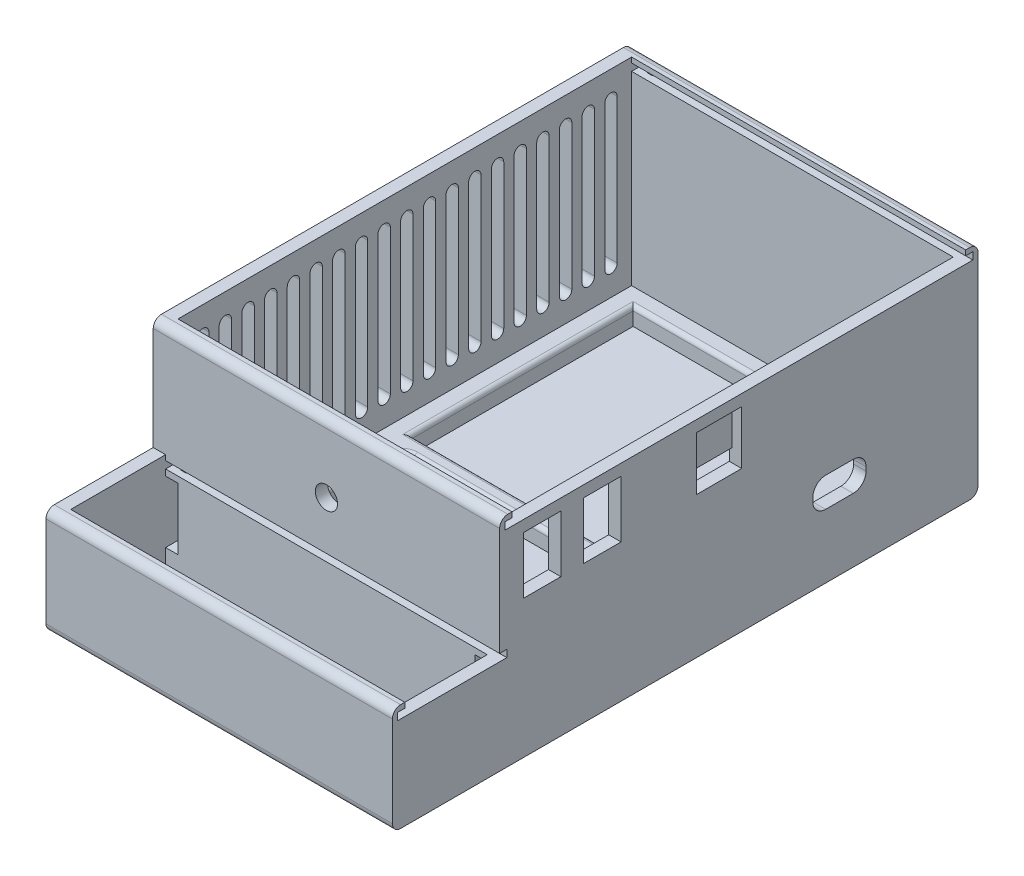
SolidWorks part; units mm, degrees
ref_plane "Front Plane" through (0, 0, 0) normal (0, 0, 1) x (1, 0, 0)
ref_plane "Top Plane" through (0, 0, 0) normal (0, 1, 0) x (1, 0, 0)
ref_plane "Right Plane" through (0, 0, 0) normal (1, 0, 0) x (0, 0, -1)
sketch "Sketch1" plane through (0, 0, 0) normal (0, 1, 0) x (1, 0, 0)
  line L5 (0, 0) -> (100, 0)
  line L6 (0, 0) -> (0, 150)
  line L7 (0, 150) -> (100, 150)
  line L8 (100, 0) -> (100, 150)
  dimension "D1" = 100
  dimension "D2" = 150
extrude "Boss-Extrude1" add sketch "Sketch1" against normal blind 5
sketch "Sketch2" plane through (0, 0, 0) normal (0, 1, 0) x (1, 0, 0)
  line L0 (0, 150) -> (0, 0) construction
  line L1 (11, 11) -> (89, 11)
  line L2 (11, 11) -> (11, 34)
  line L3 (11, 34) -> (89, 34)
  line L4 (89, 11) -> (89, 34)
  line L5 (0, 0) -> (100, 0) construction
  dimension "D1" = 78
  dimension "D2" = 23
  dimension "D3" = 11
  dimension "D4" = 11
extrude "Cut-Extrude1" cut sketch "Sketch2" against normal blind 2.5
sketch "Sketch3" plane through (0, 0, 0) normal (0, 1, 0) x (1, 0, 0)
  line L0 (11, 34) -> (89, 34)
  line L1 (89, 34) -> (89, 11)
  line L2 (89, 11) -> (11, 11)
  line L3 (11, 11) -> (11, 34)
  line L4 (8, 8) -> (8, 37)
  line L5 (8, 37) -> (92, 37)
  line L6 (92, 37) -> (92, 8)
  line L7 (92, 8) -> (8, 8)
  dimension "D1" = 3
extrude "Boss-Extrude2" add sketch "Sketch3" along normal blind 18
sketch "Sketch4" plane through (0, 0, 0) normal (0, 1, 0) x (1, 0, 0)
  line L0 (17.27, 44) -> (79.94, 44)
  line L1 (79.94, 44) -> (79.94, 46.79) construction
  line L2 (82.73, 46.79) -> (82.73, 82.03)
  line L3 (92, 37) -> (8, 37) construction
  line L4 (82.73, 82.03) -> (79.94, 82.03) construction
  line L5 (17.27, 44) -> (17.27, 82.0525)
  line L7 (17.27, 82.0525) -> (20.06, 82.0525) construction
  line L8 (17.27, 63.0262) -> (0, 63.0262) construction
  line L9 (20.06, 84.8425) -> (79.94, 84.82)
  line L10 (20.06, 84.8425) -> (20.06, 82.0525) construction
  line L11 (79.94, 82.03) -> (79.94, 84.82) construction
  line L13 (0, 150) -> (0, 0) construction
  line L14 (82.73, 64.41) -> (100, 64.41) construction
  line L15 (100, 0) -> (100, 150) construction
  arc A0 (79.94, 44) -> (82.73, 46.79) centre (79.94, 46.79) ccw
  arc A1 (82.73, 82.03) -> (79.94, 84.82) centre (79.94, 82.03) ccw
  arc A5 (17.27, 82.0525) -> (20.06, 84.8425) centre (20.06, 82.0525) cw
  dimension "D1" = 62.67
  dimension "D2" = 2.79
  dimension "D3" = 35.24
  dimension "D4" = 7
  dimension "D5" = 2.79
  dimension "D7" = 2.79
  dimension "D8" = 38.0525
extrude "Cut-Extrude2" cut sketch "Sketch4" against normal blind 4.25 contours L0 A0 L2 A1 L9 A5 L5
sketch "Sketch7" plane through (0, -2.5, 0) normal (0, 1, 0) x (1, 0, 0)
  line L0 (11, 34) -> (34, 11)
  line L1 (11, 11) -> (89, 11) construction
  line L2 (12, 34) -> (35, 11)
  line L3 (12, 34) -> (13, 34)
  line L5 (11, 11) -> (11.5217, 11)
  line L6 (89, 34) -> (89, 33)
  line L7 (13, 34) -> (36, 11)
  line L8 (14, 34) -> (37, 11)
  line L9 (15, 34) -> (38, 11)
  line L10 (16, 34) -> (39, 11)
  line L11 (17, 34) -> (40, 11)
  line L12 (18, 34) -> (41, 11)
  line L13 (19, 34) -> (42, 11)
  line L14 (20, 34) -> (43, 11)
  line L15 (21, 34) -> (44, 11)
  line L16 (22, 34) -> (45, 11)
  line L17 (23, 34) -> (46, 11)
  line L18 (24, 34) -> (47, 11)
  line L19 (25, 34) -> (48, 11)
  line L20 (26, 34) -> (49, 11)
  line L21 (27, 34) -> (50, 11)
  line L22 (28, 34) -> (51, 11)
  line L23 (29, 34) -> (52, 11)
  line L24 (30, 34) -> (53, 11)
  line L25 (31, 34) -> (54, 11)
  line L26 (32, 34) -> (55, 11)
  line L27 (33, 34) -> (56, 11)
  line L28 (34, 34) -> (57, 11)
  line L29 (35, 34) -> (58, 11)
  line L30 (36, 34) -> (59, 11)
  line L31 (37, 34) -> (60, 11)
  line L32 (38, 34) -> (61, 11)
  line L33 (39, 34) -> (62, 11)
  line L34 (40, 34) -> (63, 11)
  line L35 (41, 34) -> (64, 11)
  line L36 (42, 34) -> (65, 11)
  line L37 (43, 34) -> (66, 11)
  line L38 (44, 34) -> (67, 11)
  line L39 (45, 34) -> (68, 11)
  line L40 (46, 34) -> (69, 11)
  line L41 (47, 34) -> (70, 11)
  line L42 (48, 34) -> (71, 11)
  line L43 (49, 34) -> (72, 11)
  line L44 (50, 34) -> (73, 11)
  line L45 (51, 34) -> (74, 11)
  line L46 (52, 34) -> (75, 11)
  line L47 (53, 34) -> (76, 11)
  line L48 (54, 34) -> (77, 11)
  line L49 (55, 34) -> (78, 11)
  line L50 (56, 34) -> (79, 11)
  line L51 (57, 34) -> (80, 11)
  line L52 (58, 34) -> (81, 11)
  line L53 (59, 34) -> (82, 11)
  line L54 (60, 34) -> (83, 11)
  line L55 (61, 34) -> (84, 11)
  line L56 (62, 34) -> (85, 11)
  line L57 (63, 34) -> (86, 11)
  line L58 (64, 34) -> (87, 11)
  line L59 (65, 34) -> (88, 11)
  line L60 (66, 34) -> (89, 11)
  line L61 (67, 34) -> (89, 12)
  line L62 (68, 34) -> (89, 13)
  line L63 (69, 34) -> (89, 14)
  line L64 (70, 34) -> (89, 15)
  line L65 (71, 34) -> (89, 16)
  line L66 (72, 34) -> (89, 17)
  line L67 (73, 34) -> (89, 18)
  line L68 (74, 34) -> (89, 19)
  line L69 (75, 34) -> (89, 20)
  line L70 (76, 34) -> (89, 21)
  line L71 (77, 34) -> (89, 22)
  line L72 (78, 34) -> (89, 23)
  line L73 (79, 34) -> (89, 24)
  line L74 (80, 34) -> (89, 25)
  line L75 (81, 34) -> (89, 26)
  line L76 (82, 34) -> (89, 27)
  line L77 (83, 34) -> (89, 28)
  line L78 (84, 34) -> (89, 29)
  line L79 (85, 34) -> (89, 30)
  line L80 (86, 34) -> (89, 31)
  line L81 (87, 34) -> (89, 32)
  line L82 (88, 34) -> (89, 33)
  line L83 (11, 32.9783) -> (32.9783, 11)
  line L84 (11, 31.9565) -> (31.9565, 11)
  line L85 (11, 30.9348) -> (30.9348, 11)
  line L86 (11, 29.913) -> (29.913, 11)
  line L87 (11, 28.8913) -> (28.8913, 11)
  line L88 (11, 27.8696) -> (27.8696, 11)
  line L89 (11, 26.8478) -> (26.8478, 11)
  line L90 (11, 25.8261) -> (25.8261, 11)
  line L91 (11, 24.8043) -> (24.8043, 11)
  line L92 (11, 23.7826) -> (23.7826, 11)
  line L93 (11, 22.7609) -> (22.7609, 11)
  line L94 (11, 21.7391) -> (21.7391, 11)
  line L95 (11, 20.7174) -> (20.7174, 11)
  line L96 (11, 19.6956) -> (19.6956, 11)
  line L97 (11, 18.6739) -> (18.6739, 11)
  line L98 (11, 17.6522) -> (17.6522, 11)
  line L99 (11, 16.6304) -> (16.6304, 11)
  line L100 (11, 15.6087) -> (15.6087, 11)
  line L101 (11, 14.5869) -> (14.5869, 11)
  line L102 (11, 13.5652) -> (13.5652, 11)
  line L103 (11, 12.5435) -> (12.5435, 11)
  line L104 (11, 11.5217) -> (11.5217, 11)
  line L105 (12.5435, 11) -> (13.5652, 11)
  line L106 (11, 11.5217) -> (11, 11)
  line L107 (14.5869, 11) -> (15.6087, 11)
  line L108 (11, 13.5652) -> (11, 12.5435)
  line L110 (16.6304, 11) -> (17.6522, 11)
  line L111 (11, 16.6304) -> (11, 17.6522)
  line L112 (11, 18.6739) -> (11, 19.6956)
  line L113 (18.6739, 11) -> (19.6956, 11)
  line L114 (20.7174, 11) -> (21.7391, 11)
  line L115 (11, 20.7174) -> (11, 21.7391)
  line L116 (22.7609, 11) -> (23.7826, 11)
  line L117 (11, 22.7609) -> (11, 23.7826)
  line L118 (11, 24.8043) -> (11, 25.8261)
  line L119 (24.8043, 11) -> (25.8261, 11)
  line L120 (26.8478, 11) -> (27.8696, 11)
  line L121 (11, 26.8478) -> (11, 27.8696)
  line L122 (11, 28.8913) -> (11, 29.913)
  line L123 (11, 30.9348) -> (11, 31.9565)
  line L124 (28.8913, 11) -> (29.913, 11)
  line L125 (30.9348, 11) -> (31.9565, 11)
  line L126 (32.9783, 11) -> (34, 11)
  line L127 (35, 11) -> (36, 11)
  line L128 (11, 32.9783) -> (11, 34)
  line L129 (14, 34) -> (15, 34)
  line L130 (16, 34) -> (17, 34)
  line L131 (37, 11) -> (38, 11)
  line L132 (39, 11) -> (40, 11)
  line L133 (41, 11) -> (42, 11)
  line L134 (43, 11) -> (44, 11)
  line L135 (45, 11) -> (46, 11)
  line L136 (47, 11) -> (48, 11)
  line L137 (49, 11) -> (50, 11)
  line L138 (51, 11) -> (52, 11)
  line L139 (53, 11) -> (54, 11)
  line L140 (55, 11) -> (56, 11)
  line L141 (57, 11) -> (58, 11)
  line L142 (59, 11) -> (60, 11)
  line L143 (61, 11) -> (62, 11)
  line L144 (63, 11) -> (64, 11)
  line L145 (65, 11) -> (66, 11)
  line L146 (18, 34) -> (19, 34)
  line L147 (20, 34) -> (21, 34)
  line L148 (22, 34) -> (23, 34)
  line L149 (24, 34) -> (25, 34)
  line L150 (26, 34) -> (27, 34)
  line L151 (28, 34) -> (29, 34)
  line L152 (30, 34) -> (31, 34)
  line L153 (32, 34) -> (33, 34)
  line L154 (34, 34) -> (35, 34)
  line L155 (36, 34) -> (37, 34)
  line L156 (38, 34) -> (39, 34)
  line L157 (40, 34) -> (41, 34)
  line L158 (42, 34) -> (43, 34)
  line L159 (44, 34) -> (45, 34)
  line L160 (46, 34) -> (47, 34)
  line L161 (67, 11) -> (68, 11)
  line L162 (69, 11) -> (70, 11)
  line L163 (71, 11) -> (72, 11)
  line L164 (73, 11) -> (74, 11)
  line L165 (75, 11) -> (76, 11)
  line L166 (77, 11) -> (78, 11)
  line L167 (79, 11) -> (80, 11)
  line L168 (81, 11) -> (82, 11)
  line L169 (83, 11) -> (84, 11)
  line L170 (85, 11) -> (86, 11)
  line L171 (87, 11) -> (88, 11)
  line L172 (48, 34) -> (49, 34)
  line L173 (50, 34) -> (51, 34)
  line L174 (52, 34) -> (53, 34)
  line L175 (54, 34) -> (55, 34)
  line L176 (56, 34) -> (57, 34)
  line L177 (58, 34) -> (59, 34)
  line L178 (60, 34) -> (61, 34)
  line L179 (62, 34) -> (63, 34)
  line L180 (64, 34) -> (65, 34)
  line L181 (66, 34) -> (67, 34)
  line L182 (68, 34) -> (69, 34)
  line L183 (70, 34) -> (71, 34)
  line L184 (72, 34) -> (73, 34)
  line L185 (74, 34) -> (75, 34)
  line L186 (76, 34) -> (77, 34)
  line L187 (78, 34) -> (79, 34)
  line L188 (80, 34) -> (81, 34)
  line L189 (82, 34) -> (83, 34)
  line L190 (84, 34) -> (85, 34)
  line L191 (86, 34) -> (87, 34)
  line L192 (88, 34) -> (89, 34)
  line L193 (89, 12) -> (89, 11)
  line L194 (89, 14) -> (89, 13)
  line L195 (89, 16) -> (89, 15)
  line L196 (89, 18) -> (89, 17)
  line L197 (89, 20) -> (89, 19)
  line L198 (89, 22) -> (89, 21)
  line L199 (89, 24) -> (89, 23)
  line L200 (89, 26) -> (89, 25)
  line L201 (89, 28) -> (89, 27)
  line L202 (89, 30) -> (89, 29)
  line L203 (89, 32) -> (89, 31)
  line L204 (11, 15.6087) -> (11, 14.5869)
  dimension "D1" = 78
  dimension "D2" = 23
extrude "Cut-Extrude3" cut sketch "Sketch7" against normal blind 0.5
sketch "Sketch8" plane through (0, 0, -37) normal (0, 0, -1) x (-1, 0, 0)
  line L0 (-92, 18) -> (-92, 0) construction
  line L1 (-89, 1.5) -> (-86, 1.5)
  line L2 (-89, 1.5) -> (-89, 16.5)
  line L3 (-89, 16.5) -> (-86, 16.5)
  line L4 (-86, 1.5) -> (-86, 16.5)
  line L5 (-92, 18) -> (-8, 18) construction
  line L6 (-92, 0) -> (-8, 0) construction
  line L7 (-92, 18) -> (-8, 18) construction
  line L8 (-50, 18) -> (-50, 0) construction
  line L9 (-11, 16.5) -> (-14, 16.5)
  line L10 (-14, 1.5) -> (-14, 16.5)
  line L11 (-11, 1.5) -> (-14, 1.5)
  line L12 (-11, 1.5) -> (-11, 16.5)
  dimension "D1" = 3
  dimension "D2" = 1.5
  dimension "D3" = 1.5
  dimension "D4" = 3
extrude "Cut-Extrude4" cut sketch "Sketch8" against normal blind 3
sketch "Sketch9" plane through (8, 0, 0) normal (-1, 0, 0) x (0, 0, 1)
  line L0 (-37, 18) -> (-8, 18)
  line L1 (-8, 18) -> (-8, 21)
  line L2 (-8, 21) -> (-37, 21)
  line L3 (-37, 21) -> (-37, 18)
  dimension "D1" = 3
extrude "Boss-Extrude4" add sketch "Sketch9" against normal blind 3
sketch "Sketch10" plane through (11, 0, 0) normal (1, 0, 0) x (0, 0, -1)
  line L0 (9.25, 18) -> (8, 18)
  line L1 (8, 18) -> (8, 21)
  line L2 (8, 21) -> (11, 21)
  line L3 (8, 21) -> (37, 21) construction
  line L8 (11, 19.75) -> (11, 21)
  line L9 (11, 19.75) -> (9.25, 19.75)
  line L10 (9.25, 19.75) -> (9.25, 18)
  line L12 (8, 18) -> (37, 18) construction
  line L13 (22.5, 21) -> (22.5, 12.8527) construction
  line L22 (35.75, 19.75) -> (35.75, 18)
  line L23 (11, -3) -> (11, 18) construction
  line L24 (34, 19.75) -> (35.75, 19.75)
  line L25 (34, 19.75) -> (34, 21)
  line L26 (37, 21) -> (34, 21)
  line L27 (37, 18) -> (37, 21)
  line L28 (35.75, 18) -> (37, 18)
  dimension "D1" = 1.25
  dimension "D2" = 1.25
extrude "Boss-Extrude5" add sketch "Sketch10" along normal up to surface (81 mm away) up to face at (92, 9, -22.5)
sketch "Sketch12" plane through (0, 0, 0) normal (0, 1, 0) x (1, 0, 0)
  line L0 (0, 0) -> (100, 0)
  line L1 (100, 0) -> (100, 150)
  line L2 (100, 0) -> (100, 150) construction
  line L3 (92, 37) -> (92, 150) construction
  line L4 (100, 150) -> (0, 150) construction
  line L5 (8, 37) -> (8, 150) construction
  line L6 (100, 150) -> (92, 150)
  line L7 (92, 150) -> (92, 8)
  line L8 (92, 8) -> (8, 8)
  line L9 (8, 8) -> (8, 150)
  line L10 (8, 150) -> (0, 150)
  line L11 (0, 150) -> (0, 0)
extrude "Cut-Extrude5" cut sketch "Sketch12" against normal up to surface (5 mm away) up to face at (50, -5, -75)
sketch "Sketch13" plane through (0, 0, 0) normal (0, 1, 0) x (1, 0, 0)
  line L0 (8, 37) -> (8, 150)
  line L1 (8, 150) -> (92, 150)
  line L2 (92, 150) -> (92, 37)
  line L5 (11, 40) -> (11, 147)
  line L6 (11, 147) -> (89, 147)
  line L7 (89, 147) -> (89, 40)
  line L8 (11, 40) -> (11, 37)
  line L9 (89, 40) -> (89, 37)
  line L10 (11, 37) -> (8, 37)
  line L11 (89, 40) -> (11, 40) construction
  line L12 (92, 37) -> (8, 37) construction
  line L13 (89, 37) -> (92, 37)
  dimension "D1" = 3
extrude "Boss-Extrude6" add sketch "Sketch13" along normal blind 45
sketch "Sketch14" plane through (0, 0, 0) normal (0, 1, 0) x (1, 0, 0)
  line L11 (84.25, 142.6156) -> (15.75, 142.6156)
  line L16 (15.75, 89.2156) -> (84.25, 89.2156)
  line L17 (84.25, 89.2156) -> (84.25, 142.6156)
  line L19 (20.06, 84.8425) -> (79.94, 84.82) construction
  line L20 (84.25, 92) -> (89, 92) construction
  line L21 (89, 37) -> (89, 147) construction
  line L22 (50, 89.2156) -> (50, 84.8312) construction
  line L23 (20.06, 84.8425) -> (79.94, 84.82) construction
  line L24 (50, 147) -> (50, 142.6156) construction
  line L25 (89, 147) -> (11, 147) construction
  line L27 (15.75, 89.2156) -> (15.75, 142.6156)
  dimension "D1" = 68.5
  dimension "D7" = 53.4
extrude "Cut-Extrude6" cut sketch "Sketch14" against normal blind 4.25
sketch "Sketch46" plane through (0, 0, 0) normal (0, 1, 0) x (1, 0, 0)
  line L0 (15.5, 142.8656) -> (15.5, 88.9656)
  line L1 (15.75, 142.6156) -> (84.25, 142.6156)
  line L2 (15.75, 142.6156) -> (15.75, 89.2156)
  line L3 (15.75, 89.2156) -> (84.25, 89.2156)
  line L4 (84.25, 142.6156) -> (84.25, 89.2156)
  line L5 (15.5, 88.9656) -> (84.5, 88.9656)
  line L6 (84.5, 142.8656) -> (84.5, 88.9656)
  line L7 (15.5, 142.8656) -> (84.5, 142.8656)
  dimension "D1" = 0.25
extrude "Cut-Extrude25" cut sketch "Sketch46" against normal up to surface (4.25 mm away) up to face at (50, -4.25, -115.9156)
sketch "Sketch15" plane through (0, 21, 0) normal (0, 1, 0) x (1, 0, 0)
  line L6 (8, 37) -> (92, 37)
  line L7 (8, 37) -> (8, 34)
  line L8 (8, 34) -> (92, 34)
  line L9 (92, 37) -> (92, 34)
extrude "Boss-Extrude7" add sketch "Sketch15" along normal up to surface (24 mm away) up to face at (50, 45, -92.75)
sketch "Sketch16" plane through (0, 45, 0) normal (0, 1, 0) x (1, 0, 0)
  line L16 (92, 34) -> (8, 34)
  line L17 (8, 34) -> (8, 150)
  line L18 (8, 150) -> (92, 150)
  line L19 (11, 37) -> (92, 37)
  line L20 (92, 34) -> (92, 150) construction
  line L21 (92, 34) -> (92, 37)
  line L22 (11, 37) -> (11, 147)
  line L23 (11, 147) -> (92, 147)
  line L24 (92, 147) -> (92, 150)
extrude "Boss-Extrude8" add sketch "Sketch16" along normal blind 3
sketch "Sketch19" plane through (92, 0, 0) normal (1, 0, 0) x (0, 0, -1)
  line L0 (37, 46.75) -> (35.25, 46.75)
  line L1 (37, 48) -> (37, 45) construction
  line L2 (35.25, 46.75) -> (35.25, 45)
  line L3 (35.25, 45) -> (37, 45)
  line L4 (37, 45) -> (37, 46.75)
  line L5 (92, 45) -> (92, 48) construction
  line L6 (37, 45) -> (147, 45) construction
  line L7 (147, 45) -> (147, 46.75)
  line L8 (148.75, 45) -> (147, 45)
  line L9 (148.75, 46.75) -> (148.75, 45)
  line L10 (147, 46.75) -> (148.75, 46.75)
  line L11 (34, 48) -> (37, 48) construction
  line L12 (34, 19.75) -> (34, 48) construction
  dimension "D1" = 1.25
  dimension "D2" = 1.25
  dimension "D4" = 3
extrude "Cut-Extrude8" cut sketch "Sketch19" against normal up to surface (81 mm away) up to face at (11, 3.0077, -27.5846)
sketch "Sketch23" plane through (0, 0, -9.25) normal (0, 0, -1) x (-1, 0, 0)
  line L0 (-11, 18.875) -> (-14, 18.875) construction
  line L1 (-11, 18) -> (-11, 19.75) construction
  line L3 (-14.875, 19.5) -> (-13.125, 19.5)
  line L4 (-14.875, 19.5) -> (-14.875, 18.25)
  line L5 (-14.875, 18.25) -> (-13.125, 18.25)
  line L6 (-13.125, 19.5) -> (-13.125, 18.25)
  line L7 (-14.875, 19.5) -> (-13.125, 18.25) construction
  line L8 (-14.875, 18.25) -> (-13.125, 19.5) construction
  dimension "D1" = 3
  dimension "D2" = 1.75
  dimension "D3" = 1.25
extrude "Boss-Extrude9" add sketch "Sketch23" along normal blind 0.4
fillet "Fillet2" radius 0.4 2 edges at (13.125, 18.875, -9.65) (14.875, 18.875, -9.65)
sketch "Sketch40" plane through (0, 0, -35.75) normal (0, 0, 1) x (1, 0, 0)
  line L0 (11, 18.875) -> (14, 18.875) construction
  line L1 (11, 19.75) -> (11, 18) construction
  line L3 (13.125, 19.5) -> (14.875, 19.5)
  line L4 (13.125, 19.5) -> (13.125, 18.25)
  line L5 (13.125, 18.25) -> (14.875, 18.25)
  line L6 (14.875, 19.5) -> (14.875, 18.25)
  line L7 (13.125, 19.5) -> (14.875, 18.25) construction
  line L8 (13.125, 18.25) -> (14.875, 19.5) construction
  dimension "D1" = 3
  dimension "D2" = 1.25
  dimension "D3" = 1.75
extrude "Boss-Extrude14" add sketch "Sketch40" along normal blind 0.4
fillet "Fillet6" radius 0.4 2 edges at (14.875, 18.875, -35.35) (13.125, 18.875, -35.35)
sketch "Sketch25" plane through (0, 0, -35.25) normal (0, 0, -1) x (-1, 0, 0)
  line L0 (-11, 45.875) -> (-14, 45.875) construction
  line L1 (-11, 46.75) -> (-11, 45) construction
  line L3 (-13.125, 46.5) -> (-14.875, 46.5)
  line L4 (-13.125, 46.5) -> (-13.125, 45.25)
  line L5 (-13.125, 45.25) -> (-14.875, 45.25)
  line L6 (-14.875, 46.5) -> (-14.875, 45.25)
  line L7 (-13.125, 46.5) -> (-14.875, 45.25) construction
  line L8 (-13.125, 45.25) -> (-14.875, 46.5) construction
  dimension "D1" = 3
  dimension "D2" = 1.75
  dimension "D3" = 1.25
extrude "Boss-Extrude11" add sketch "Sketch25" along normal blind 0.4
fillet "Fillet4" radius 0.4 2 edges at (13.125, 45.875, -35.65) (14.875, 45.875, -35.65)
sketch "Sketch26" plane through (0, 0, -148.75) normal (0, 0, 1) x (1, 0, 0)
  line L0 (11, 45.875) -> (14, 45.875) construction
  line L1 (11, 45) -> (11, 46.75) construction
  line L3 (13.125, 46.5) -> (14.875, 46.5)
  line L4 (13.125, 46.5) -> (13.125, 45.25)
  line L5 (13.125, 45.25) -> (14.875, 45.25)
  line L6 (14.875, 46.5) -> (14.875, 45.25)
  line L7 (13.125, 46.5) -> (14.875, 45.25) construction
  line L8 (13.125, 45.25) -> (14.875, 46.5) construction
  dimension "D1" = 3
  dimension "D2" = 1.75
  dimension "D3" = 1.25
extrude "Boss-Extrude12" add sketch "Sketch26" along normal blind 0.4
fillet "Fillet5" radius 0.4 2 edges at (13.125, 45.875, -148.35) (14.875, 45.875, -148.35)
sketch "Sketch27" plane through (92, 0, 0) normal (1, 0, 0) x (0, 0, -1)
  line L0 (34, 19.75) -> (34, 48) construction
  line L1 (82, 42) -> (92.45, 42)
  line L2 (82, 42) -> (82, 29.5)
  line L3 (82, 29.5) -> (92.45, 29.5)
  line L4 (92.45, 42) -> (92.45, 29.5)
  line L7 (35.25, 45) -> (148.75, 45) construction
  dimension "D1" = 12.5
  dimension "D2" = 10.45
  dimension "D3" = 48
  dimension "D4" = 3
extrude "Cut-Extrude10" cut sketch "Sketch27" against normal up to surface (3 mm away) up to face at (89, 0.5702, -28.0877)
sketch "Sketch29" plane through (92, 0, 0) normal (1, 0, 0) x (0, 0, -1)
  line L0 (34, 19.75) -> (34, 48) construction
  line L1 (40, 42) -> (48.6, 42)
  line L2 (40, 42) -> (40, 28.7)
  line L3 (40, 28.7) -> (48.6, 28.7)
  line L4 (48.6, 42) -> (48.6, 28.7)
  line L5 (54.6, 42) -> (63.2, 42)
  line L6 (54.6, 42) -> (54.6, 28.7)
  line L7 (54.6, 28.7) -> (63.2, 28.7)
  line L8 (63.2, 42) -> (63.2, 28.7)
  line L10 (35.25, 45) -> (148.75, 45) construction
  dimension "D1" = 8.6
  dimension "D2" = 8.6
  dimension "D3" = 13.3
  dimension "D4" = 13.3
  dimension "D5" = 6
  dimension "D6" = 6
  dimension "D7" = 3
extrude "Cut-Extrude11" cut sketch "Sketch29" against normal up to surface (3 mm away) up to face at (89, 35.75, -87.225)
sketch "Sketch30" plane through (0, 0, -34) normal (0, 0, 1) x (1, 0, 0)
  line L0 (92, 18) -> (8, 48) construction
  line L1 (92, 19.75) -> (92, 48) construction
  line L2 (50, 33) -> (50, 31.5) construction
  circle A2 centre (50, 31.5) radius 2.5
  dimension "D1" = 1.5
  dimension "D2" = 5
extrude "Cut-Extrude12" cut sketch "Sketch30" against normal up to surface (3 mm away) up to face at (50, 13.5, -37)
sketch "Sketch31" plane through (92, 0, 0) normal (1, 0, 0) x (0, 0, -1)
  line L0 (150, -5) -> (8, -5) construction
  line L1 (113.05, 12.5) -> (119.75, 12.5)
  line L2 (111.95, 13.6) -> (111.95, 14.55)
  line L3 (113.05, 15.65) -> (119.75, 15.65)
  line L4 (120.85, 13.6) -> (120.85, 14.55)
  line L5 (150, -5) -> (150, 48) construction
  arc A0 (119.75, 15.65) -> (120.85, 14.55) centre (119.75, 14.55) cw
  arc A1 (119.75, 12.5) -> (120.85, 13.6) centre (119.75, 13.6) ccw
  arc A2 (113.05, 12.5) -> (111.95, 13.6) centre (113.05, 13.6) cw
  arc A3 (111.95, 14.55) -> (113.05, 15.65) centre (113.05, 14.55) cw
  point P14 (120.85, 12.5)
  point P17 (111.95, 12.5)
  dimension "D5" = 1.1
  dimension "D1" = 0.95
  dimension "D2" = 29.15
  dimension "D3" = 17.5
  dimension "D4" = 6.7
extrude "Cut-Extrude13" cut sketch "Sketch31" against normal up to surface (3 mm away) up to face at (89, 35.35, -44.3)
sketch "Sketch33" plane through (11, 0, 0) normal (1, 0, 0) x (0, 0, -1)
  line L0 (142, 6.5) -> (142, 41.5) construction
  line L1 (140.5, 6.5) -> (140.5, 41.5)
  line L2 (143.5, 6.5) -> (143.5, 41.5)
  line L3 (147, 45) -> (147, 0) construction
  line L5 (142, 5) -> (142, 0) construction
  line L6 (37, 0) -> (147, 0) construction
  line L7 (142, 43) -> (142, 48) construction
  line L8 (136.5, 6.5) -> (136.5, 41.5) construction
  line L9 (135, 6.5) -> (135, 41.5)
  line L10 (138, 6.5) -> (138, 41.5)
  line L11 (131, 6.5) -> (131, 41.5) construction
  line L12 (129.5, 6.5) -> (129.5, 41.5)
  line L13 (132.5, 6.5) -> (132.5, 41.5)
  line L14 (125.5, 6.5) -> (125.5, 41.5) construction
  line L15 (124, 6.5) -> (124, 41.5)
  line L16 (127, 6.5) -> (127, 41.5)
  line L17 (120, 6.5) -> (120, 41.5) construction
  line L18 (118.5, 6.5) -> (118.5, 41.5)
  line L19 (121.5, 6.5) -> (121.5, 41.5)
  line L20 (114.5, 6.5) -> (114.5, 41.5) construction
  line L21 (113, 6.5) -> (113, 41.5)
  line L22 (116, 6.5) -> (116, 41.5)
  line L23 (109, 6.5) -> (109, 41.5) construction
  line L24 (107.5, 6.5) -> (107.5, 41.5)
  line L25 (110.5, 6.5) -> (110.5, 41.5)
  line L26 (103.5, 6.5) -> (103.5, 41.5) construction
  line L27 (102, 6.5) -> (102, 41.5)
  line L28 (105, 6.5) -> (105, 41.5)
  line L29 (98, 6.5) -> (98, 41.5) construction
  line L30 (96.5, 6.5) -> (96.5, 41.5)
  line L31 (99.5, 6.5) -> (99.5, 41.5)
  line L32 (92.5, 6.5) -> (92.5, 41.5) construction
  line L33 (91, 6.5) -> (91, 41.5)
  line L34 (94, 6.5) -> (94, 41.5)
  line L35 (87, 6.5) -> (87, 41.5) construction
  line L36 (85.5, 6.5) -> (85.5, 41.5)
  line L37 (88.5, 6.5) -> (88.5, 41.5)
  line L38 (81.5, 6.5) -> (81.5, 41.5) construction
  line L39 (80, 6.5) -> (80, 41.5)
  line L40 (83, 6.5) -> (83, 41.5)
  line L41 (76, 6.5) -> (76, 41.5) construction
  line L42 (74.5, 6.5) -> (74.5, 41.5)
  line L43 (77.5, 6.5) -> (77.5, 41.5)
  line L44 (70.5, 6.5) -> (70.5, 41.5) construction
  line L45 (69, 6.5) -> (69, 41.5)
  line L46 (72, 6.5) -> (72, 41.5)
  line L47 (65, 6.5) -> (65, 41.5) construction
  line L48 (63.5, 6.5) -> (63.5, 41.5)
  line L49 (66.5, 6.5) -> (66.5, 41.5)
  line L50 (59.5, 6.5) -> (59.5, 41.5) construction
  line L51 (58, 6.5) -> (58, 41.5)
  line L52 (61, 6.5) -> (61, 41.5)
  line L53 (54, 6.5) -> (54, 41.5) construction
  line L54 (52.5, 6.5) -> (52.5, 41.5)
  line L55 (55.5, 6.5) -> (55.5, 41.5)
  line L56 (48.5, 6.5) -> (48.5, 41.5) construction
  line L57 (47, 6.5) -> (47, 41.5)
  line L58 (50, 6.5) -> (50, 41.5)
  line L59 (43, 6.5) -> (43, 41.5) construction
  line L60 (41.5, 6.5) -> (41.5, 41.5)
  line L61 (44.5, 6.5) -> (44.5, 41.5)
  line L62 (37, 48) -> (147, 48) construction
  arc A0 (140.5, 6.5) -> (143.5, 6.5) centre (142, 6.5) ccw
  arc A1 (143.5, 41.5) -> (140.5, 41.5) centre (142, 41.5) ccw
  arc A2 (135, 6.5) -> (138, 6.5) centre (136.5, 6.5) ccw
  arc A3 (138, 41.5) -> (135, 41.5) centre (136.5, 41.5) ccw
  arc A4 (129.5, 6.5) -> (132.5, 6.5) centre (131, 6.5) ccw
  arc A5 (132.5, 41.5) -> (129.5, 41.5) centre (131, 41.5) ccw
  arc A6 (124, 6.5) -> (127, 6.5) centre (125.5, 6.5) ccw
  arc A7 (127, 41.5) -> (124, 41.5) centre (125.5, 41.5) ccw
  arc A8 (118.5, 6.5) -> (121.5, 6.5) centre (120, 6.5) ccw
  arc A9 (121.5, 41.5) -> (118.5, 41.5) centre (120, 41.5) ccw
  arc A10 (113, 6.5) -> (116, 6.5) centre (114.5, 6.5) ccw
  arc A11 (116, 41.5) -> (113, 41.5) centre (114.5, 41.5) ccw
  arc A12 (107.5, 6.5) -> (110.5, 6.5) centre (109, 6.5) ccw
  arc A13 (110.5, 41.5) -> (107.5, 41.5) centre (109, 41.5) ccw
  arc A14 (102, 6.5) -> (105, 6.5) centre (103.5, 6.5) ccw
  arc A15 (105, 41.5) -> (102, 41.5) centre (103.5, 41.5) ccw
  arc A16 (96.5, 6.5) -> (99.5, 6.5) centre (98, 6.5) ccw
  arc A17 (99.5, 41.5) -> (96.5, 41.5) centre (98, 41.5) ccw
  arc A18 (91, 6.5) -> (94, 6.5) centre (92.5, 6.5) ccw
  arc A19 (94, 41.5) -> (91, 41.5) centre (92.5, 41.5) ccw
  arc A20 (85.5, 6.5) -> (88.5, 6.5) centre (87, 6.5) ccw
  arc A21 (88.5, 41.5) -> (85.5, 41.5) centre (87, 41.5) ccw
  arc A22 (80, 6.5) -> (83, 6.5) centre (81.5, 6.5) ccw
  arc A23 (83, 41.5) -> (80, 41.5) centre (81.5, 41.5) ccw
  arc A24 (74.5, 6.5) -> (77.5, 6.5) centre (76, 6.5) ccw
  arc A25 (77.5, 41.5) -> (74.5, 41.5) centre (76, 41.5) ccw
  arc A26 (69, 6.5) -> (72, 6.5) centre (70.5, 6.5) ccw
  arc A27 (72, 41.5) -> (69, 41.5) centre (70.5, 41.5) ccw
  arc A28 (63.5, 6.5) -> (66.5, 6.5) centre (65, 6.5) ccw
  arc A29 (66.5, 41.5) -> (63.5, 41.5) centre (65, 41.5) ccw
  arc A30 (58, 6.5) -> (61, 6.5) centre (59.5, 6.5) ccw
  arc A31 (61, 41.5) -> (58, 41.5) centre (59.5, 41.5) ccw
  arc A32 (52.5, 6.5) -> (55.5, 6.5) centre (54, 6.5) ccw
  arc A33 (55.5, 41.5) -> (52.5, 41.5) centre (54, 41.5) ccw
  arc A34 (47, 6.5) -> (50, 6.5) centre (48.5, 6.5) ccw
  arc A35 (50, 41.5) -> (47, 41.5) centre (48.5, 41.5) ccw
  arc A36 (41.5, 6.5) -> (44.5, 6.5) centre (43, 6.5) ccw
  arc A37 (44.5, 41.5) -> (41.5, 41.5) centre (43, 41.5) ccw
  point P2 (142, 24)
  point P21 (136.5, 24)
  point P28 (131, 24)
  point P35 (125.5, 24)
  point P42 (120, 24)
  point P49 (114.5, 24)
  point P56 (109, 24)
  point P63 (103.5, 24)
  point P70 (98, 24)
  point P77 (92.5, 24)
  point P84 (87, 24)
  point P91 (81.5, 24)
  point P98 (76, 24)
  point P105 (70.5, 24)
  point P112 (65, 24)
  point P118 (59.5, 24)
  point P125 (54, 24)
  point P132 (48.5, 24)
  point P139 (43, 24)
  dimension "D2" = 1.5
  dimension "D5" = 2.5
  dimension "D1" = 35
  dimension "D3" = 5
  dimension "D4" = 19
extrude "Cut-Extrude15" cut sketch "Sketch33" against normal up to surface (3 mm away) up to face at (8, 21.3333, -64)
sketch "Sketch34" plane through (0, 0, 0) normal (0, 1, 0) x (1, 0, 0)
  line L30 (17.02, 82.0525) -> (17.02, 43.75)
  line L31 (17.02, 43.75) -> (79.94, 43.75)
  line L32 (82.98, 46.79) -> (82.98, 82.03)
  line L33 (79.9401, 85.07) -> (20.06, 85.0925)
  line L34 (17.02, 82.0525) -> (17.02, 43.75)
  line L35 (17.02, 43.75) -> (79.94, 43.75)
  line L36 (82.98, 46.79) -> (82.98, 82.03)
  line L37 (79.9401, 85.07) -> (20.06, 85.0925)
  arc A20 (20.06, 85.0925) -> (17.02, 82.0525) centre (20.06, 82.0525) ccw
  arc A21 (79.94, 43.75) -> (82.98, 46.79) centre (79.94, 46.79) ccw
  arc A22 (82.98, 82.03) -> (79.9401, 85.07) centre (79.94, 82.03) ccw
  arc A23 (20.06, 85.0925) -> (17.02, 82.0525) centre (20.06, 82.0525) ccw
  arc A24 (79.94, 43.75) -> (82.98, 46.79) centre (79.94, 46.79) ccw
  arc A25 (82.98, 82.03) -> (79.9401, 85.07) centre (79.94, 82.03) ccw
  dimension "D1" = 0.25
extrude "Cut-Extrude16" cut sketch "Sketch34" against normal up to surface (4.25 mm away) up to face at (54.3597, -4.25, -67.0161)
sketch "Sketch36" plane through (92, 0, 0) normal (1, 0, 0) x (0, 0, -1)
  line L14 (81.75, 29.25) -> (92.7, 29.25)
  line L15 (81.75, 42.25) -> (81.75, 29.25)
  line L16 (92.7, 29.25) -> (92.7, 42.25)
  line L17 (92.7, 42.25) -> (81.75, 42.25)
  line L18 (81.75, 29.25) -> (92.7, 29.25)
  line L19 (81.75, 42.25) -> (81.75, 29.25)
  line L20 (39.75, 42.25) -> (39.75, 28.45)
  line L21 (39.75, 28.45) -> (48.85, 28.45)
  line L22 (48.85, 28.45) -> (48.85, 42.25)
  line L23 (48.85, 42.25) -> (39.75, 42.25)
  line L24 (39.75, 42.25) -> (39.75, 28.45)
  line L25 (39.75, 28.45) -> (48.85, 28.45)
  line L26 (48.85, 28.45) -> (48.85, 42.25)
  line L27 (48.85, 42.25) -> (39.75, 42.25)
  line L28 (92.7, 29.25) -> (92.7, 42.25)
  line L29 (92.7, 42.25) -> (81.75, 42.25)
  line L38 (54.35, 28.45) -> (63.45, 28.45)
  line L39 (54.35, 42.25) -> (54.35, 28.45)
  line L40 (63.45, 28.45) -> (63.45, 42.25)
  line L41 (63.45, 42.25) -> (54.35, 42.25)
  line L42 (54.35, 28.45) -> (63.45, 28.45)
  line L43 (54.35, 42.25) -> (54.35, 28.45)
  line L44 (63.45, 28.45) -> (63.45, 42.25)
  line L45 (63.45, 42.25) -> (54.35, 42.25)
  dimension "D1" = 0.25
  dimension "D2" = 0.25
  dimension "D3" = 0.25
extrude "Cut-Extrude18" cut sketch "Sketch36" against normal up to surface (3 mm away) up to face at (89, 14.075, -116.4)
sketch "Sketch37" plane through (0, 0, -34) normal (0, 0, 1) x (1, 0, 0)
  circle A2 centre (50, 31.5) radius 2.7
  circle A4 centre (50, 31.5) radius 2.7
  dimension "D1" = 0.2
extrude "Cut-Extrude19" cut sketch "Sketch37" against normal up to surface (3 mm away) up to face at (52.5, 31.5, -37)
sketch "Sketch38" plane through (89, 0, 0) normal (-1, 0, 0) x (0, 0, 1)
  line L5 (-81.75, 29.25) -> (-81.75, 42.25) construction
  line L6 (-92.7, 42.25) -> (-81.75, 42.25)
  line L7 (-92.7, 42.25) -> (-92.7, 32.39)
  line L8 (-92.7, 32.39) -> (-81.75, 32.39)
  line L9 (-81.75, 42.25) -> (-81.75, 32.39)
  line L10 (-92.7, 29.25) -> (-81.75, 29.25) construction
  dimension "D1" = 3.14
extrude "Boss-Extrude13" add sketch "Sketch38" against normal blind 0.6
sketch "Sketch39" plane through (92, 0, 0) normal (1, 0, 0) x (0, 0, -1)
  line L27 (122.85, 13.6) -> (122.85, 14.55)
  line L28 (113.05, 10.5) -> (119.75, 10.5)
  line L29 (109.95, 14.55) -> (109.95, 13.6)
  line L30 (119.75, 17.65) -> (113.05, 17.65)
  line L31 (122.85, 13.6) -> (122.85, 14.55)
  line L32 (113.05, 10.5) -> (119.75, 10.5)
  line L33 (109.95, 14.55) -> (109.95, 13.6)
  line L34 (119.75, 17.65) -> (113.05, 17.65)
  arc A20 (122.85, 14.55) -> (119.75, 17.65) centre (119.75, 14.55) ccw
  arc A21 (119.75, 10.5) -> (122.85, 13.6) centre (119.75, 13.6) ccw
  arc A22 (109.95, 13.6) -> (113.05, 10.5) centre (113.05, 13.6) ccw
  arc A23 (113.05, 17.65) -> (109.95, 14.55) centre (113.05, 14.55) ccw
  arc A24 (122.85, 14.55) -> (119.75, 17.65) centre (119.75, 14.55) ccw
  arc A25 (119.75, 10.5) -> (122.85, 13.6) centre (119.75, 13.6) ccw
  arc A26 (109.95, 13.6) -> (113.05, 10.5) centre (113.05, 13.6) ccw
  arc A27 (113.05, 17.65) -> (109.95, 14.55) centre (113.05, 14.55) ccw
  dimension "D1" = 2
extrude "Cut-Extrude20" cut sketch "Sketch39" against normal up to surface (3 mm away) up to face at (89, 35.35, -44.3)
fillet "Fillet18" radius 2 5 edges at (50, -5, -150) (50, 48, -150) (50, 48, -34) (50, -5, -8) (50, 21, -8)
fillet "Fillet19" radius 1 11 edges at (17.02, 0, -62.9012) (17.9104, 0, -84.2021) (50, 0, -85.0812) (82.0896, 0, -84.1796) (82.98, 0, -64.41) (82.0896, 0, -44.6404) (84.5, 0, -115.9156) (50, 0, -142.8656) (15.5, 0, -115.9156) (50, 0, -88.9656) (48.48, 0, -43.75)
